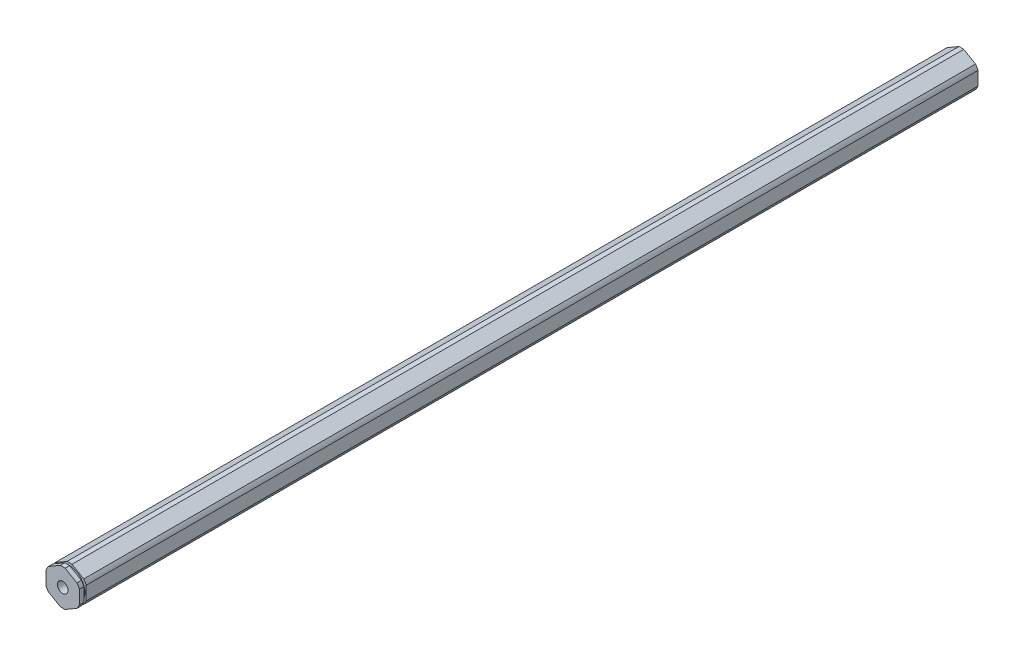
SolidWorks part; units mm, degrees
ref_plane "Front Plane" through (0, 0, 0) normal (0, 0, 1) x (1, 0, 0)
ref_plane "Top Plane" through (0, 0, 0) normal (0, 1, 0) x (1, 0, 0)
ref_plane "Right Plane" through (0, 0, 0) normal (1, 0, 0) x (0, 0, -1)
sketch "Sketch1" plane through (0, 0, 0) normal (0, 0, 1) x (1, 0, 0)
  line L1 (0, 7.3323) -> (-6.35, 3.6662)
  line L2 (-6.35, 3.6662) -> (-6.35, -3.6662)
  line L3 (-6.35, -3.6662) -> (0, -7.3323)
  line L4 (0, -7.3323) -> (6.35, -3.6662)
  line L5 (6.35, -3.6662) -> (6.35, 3.6662)
  line L6 (6.35, 3.6662) -> (0, 7.3323)
  circle A0 centre (0, 0) radius 6.35 construction
  circle A1 centre (0, 0) radius 6.858
  dimension "D1" = 12.7
  dimension "D2" = 13.716
extrude "Boss-Extrude1" add sketch "Sketch1" along normal mid plane 341.884 contours L5 A1 L6 L1 L2 L3 L4 region at (0, 0, 0)
hole_wizard "#10-32 Tapped Hole1" positions "3DSketch1" profile "Sketch2" tap size "#10-32" standard "ANSI Inch"
sketch3d "3DSketch1"
  line L0 (0, 0, 170.942) -> (0, 0, -170.942) construction
  line L1 (0, 0, 170.942) -> (0, 0, -170.942) construction
  point P0 (0, 0, 170.942)
  point P4 (0, 0, -170.942)
sketch "Sketch2" plane through (0, 0, 170.942) normal (1, 0, 0) x (0, -1, 0)
  line L0 (0, 0) -> (0, 17.5608)
  line L1 (0, 17.5608) -> (2.0193, 16.3474)
  line L2 (2.0193, 16.3474) -> (2.0193, 0)
  line L5 (2.0193, 0) -> (0, 0)
  line L10 (0, 17.5608) -> (-2.0193, 16.3474) construction
  line L11 (0, -6.35) -> (0, 107.95) construction
  dimension "Tap Drill Dia." = 4.0386
  dimension "Tap Drill Depth" = 16.3474
  dimension "Drill Angle" = 118
cosmetic thread "Hole Thread1" parameters "D1"=13.97, "D2"=4.826
cosmetic thread "Hole Thread2" parameters "D1"=13.97, "D2"=4.826
sketch "Sketch5" plane through (0, 0, 0) normal (1, 0, 0) x (0, 0, -1)
  line L0 (170.942, 6.858) -> (-170.942, 6.858) construction
  line L1 (-169.2275, 6.858) -> (-168.3385, 6.858)
  line L2 (-169.2275, 6.858) -> (-169.2275, 5.8547)
  line L3 (-169.2275, 5.8547) -> (-168.3385, 5.8547)
  line L4 (-168.3385, 6.858) -> (-168.3385, 5.8547)
  line L5 (-165.0472, 0) -> (-158.8423, 0) construction
  dimension "D1" = 5.8547
  dimension "D2" = 0.889
  dimension "D3" = 1.7145
revolve "Cut-Revolve1" cut sketch "Sketch5" angle 360 about L5
mirror "Mirror1" [suppressed] about plane through (0, 0, 0) normal (0, 0, 1)
